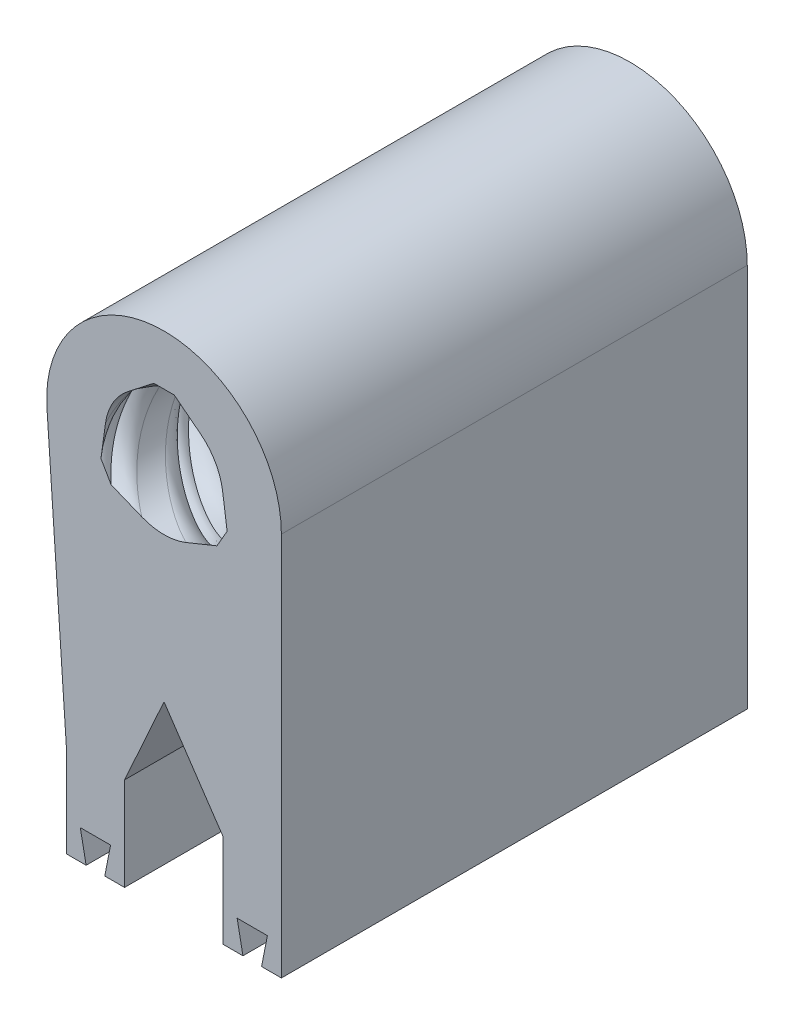
SolidWorks part; units mm, degrees
material "ABS"
ref_plane "Front Plane" through (0, 0, 0) normal (0, 0, 1) x (1, 0, 0)
ref_plane "Top Plane" through (0, 0, 0) normal (0, 1, 0) x (1, 0, 0)
ref_plane "Right Plane" through (0, 0, 0) normal (1, 0, 0) x (0, 0, -1)
sketch "Sketch1" plane through (0, 0, 0) normal (0, 0, 1) x (1, 0, 0)
  line L8 (0.5323, 28) -> (0.5323, -22)
  line L9 (-36.3977, -38) -> (-26.3977, -38)
  line L10 (-19.6177, 28) -> (-19.6177, -20.8617) construction
  line L11 (-36.3977, -38) -> (-36.3977, -22)
  line L12 (-36.3977, -22) -> (-26.3977, -22)
  line L13 (-26.3977, -38) -> (-26.3977, -22)
  line L14 (-9.4677, -38) -> (0.5323, -38)
  line L15 (-9.4677, -38) -> (-9.4677, -22)
  line L16 (-9.4677, -22) -> (0.5323, -22)
  line L17 (0.5323, -38) -> (0.5323, -22)
  line L18 (-9.4677, -22) -> (-19.6177, -7)
  line L19 (-19.6177, -7) -> (-26.3977, -22)
  line L20 (-36.3977, -22) -> (-39.7208, 26.6262)
  circle A0 centre (-19.6177, 28) radius 10.15
  circle A1 centre (-19.6177, 28) radius 20.15
  dimension "D7" = 10
  dimension "D8" = 20.3
  dimension "D1" = 16.93
  dimension "D2" = 10
  dimension "D3" = 16
  dimension "D4" = 10
  dimension "D5" = 50
  dimension "D6" = 15
extrude "Boss-Extrude1" add sketch "Sketch1" along normal blind 80 contours A1 L16 L12 | A1 L16 | A1 L16 A0 | A1 L12 L16 | A1 L16 | L16 A1 | A1 | A0 | L11 L9 L13 L12 region at (-18.9498, 8.4313, 0) region at (-18.3852, -3.2026, 0) region at (-4.4677, -30, 0)
sketch "Sketch3" plane through (0, 0, 0) normal (0, 0, -1) x (-1, 0, 0)
  line L0 (13.3834, 36.0098) -> (17.8677, 39.5)
  line L1 (17.8677, 39.5) -> (21.3677, 39.5)
  line L2 (21.3677, 39.5) -> (25.8519, 36.0098)
  circle A0 centre (19.6177, 28) radius 10.15 construction
  arc A2 (13.3834, 36.0098) -> (25.8519, 36.0098) centre (19.6177, 28) cw
  dimension "D1" = 11.5
  dimension "D2" = 1.75
  dimension "D3" = 3.5
sketch "Sketch5" plane through (0, 0, 0) normal (0, 0, -1) x (-1, 0, 0)
  circle A0 centre (19.6177, 28) radius 8
curve "Helix/Spiral1" pitch 40 height 90 radius 8 centre (-19.6177, 28, 0) axis (0, 0, 1) start towards (0, 1, 0)
sweep "Cut-Sweep3" cut profiles "Sketch3" path "Helix/Spiral1" align with end faces yes
pattern_circular "CirPattern1" count 3 over 360 about axis through (-19.6177, 28, 80) along (0, 0, -1) of "Cut-Sweep3" reverse direction yes
sketch "Sketch7" plane through (0, 0, 80) normal (0, 0, 1) x (1, 0, 0)
  line L0 (-32.9977, -38) -> (-33.9977, -32.9)
  line L1 (-36.3977, -38) -> (-26.3977, -38) construction
  line L2 (-33.9977, -32.9) -> (-28.7977, -32.9)
  line L3 (-28.7977, -32.9) -> (-29.7977, -38)
  line L4 (-31.3977, -32.9) -> (-31.3977, -38)
  line L5 (-32.9977, -38) -> (-29.7977, -38)
  line L6 (-4.4677, -38) -> (-4.4677, -32.9)
  line L7 (-9.4677, -38) -> (0.5323, -38) construction
  line L8 (-2.8677, -38) -> (-1.8677, -32.9)
  line L9 (-1.8677, -32.9) -> (-7.0677, -32.9)
  line L10 (-7.0677, -32.9) -> (-6.0677, -38)
  line L11 (-6.0677, -38) -> (-2.8677, -38)
  point P14 (0, 0)
  point P17 (0, 0)
  line M5 (-36.3977, -38) -> (-26.3977, -38)
  line M10 (-9.4677, -38) -> (0.5323, -38)
  dimension "D1" = 5.2
  dimension "D2" = 5.1
  dimension "D3" = 3.2
  dimension "D4" = 1.6
  dimension "D5" = 5.2
  dimension "D6" = 5.1
  dimension "D7" = 3.2
  dimension "D8" = 1.6
extrude "Cut-Extrude1" cut sketch "Sketch7" against normal through all contours L4 L2 L0 M5 | L2 L4 L3 M5 | L9 L10 L6 M10 | L8 L9 L6 M10 region at (-32.4675, -35.2476, 80) region at (-30.3278, -35.2476, 80) region at (-5.5375, -35.2476, 80) region at (-3.3978, -35.2476, 80)
equation "\"D1@Boss-Extrude1\"= 68.00- 6.63"
equation "\"D2@Sketch3\"=\"D3@Sketch3\"/2"
equation "\"D4@Sketch7\"=\"D3@Sketch7\"/2"
equation "\"D8@Sketch7\"=\"D7@Sketch7\"/2"
equation "\"D5@Sketch7\"=\"D1@Sketch7\""
equation "\"D7@Sketch7\"=\"D3@Sketch7\""
equation "\"D6@Sketch7\"=\"D2@Sketch7\""
